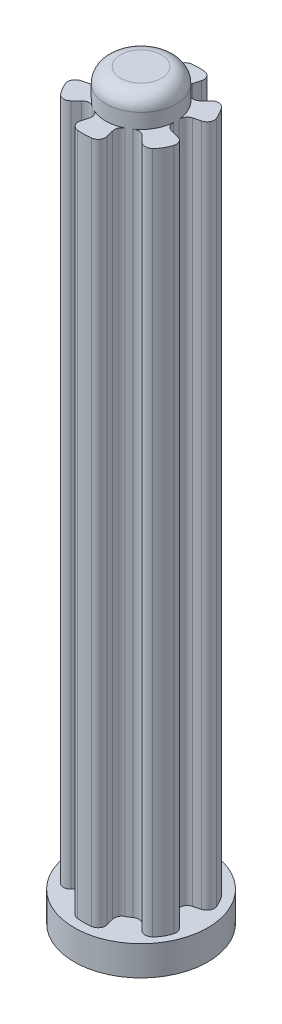
SolidWorks part; units mm, degrees
ref_plane "Front Plane" through (0, 0, 0) normal (0, 0, 1) x (1, 0, 0)
ref_plane "Top Plane" through (0, 0, 0) normal (0, 1, 0) x (1, 0, 0)
ref_plane "Right Plane" through (0, 0, 0) normal (1, 0, 0) x (0, 0, -1)
sketch "Sketch2" plane through (0, 0, 0) normal (0, 1, 0) x (1, 0, 0)
  line L0 (0, 0) -> (0.0739, 0)
  line L2 (2.3008, -0.5891) -> (3.7752, -0.9786)
  line L3 (0.0739, 0) -> (0.1042, -0.0303)
  line L4 (0, 0) -> (0.0858, -0.0446)
  line L5 (1.6802, 1.6786) -> (2.7413, 2.7388)
  line L6 (-1.6794, 1.6794) -> (-2.74, 2.74)
  line L8 (0.6147, 2.2941) -> (1.0029, 3.743)
  line L9 (-0.6147, 2.2941) -> (-1.0029, 3.743)
  line L10 (2.2941, 0.6147) -> (3.743, 1.0029)
  line L11 (0, 0) -> (0.1042, -0.0303)
  line L12 (-2.2941, 0.6147) -> (-3.743, 1.0029)
  line L13 (0.0739, 0) -> (0.0858, -0.0446)
  line L14 (-0.6147, -2.2941) -> (-1.0029, -3.743)
  line L15 (-2.2941, -0.6147) -> (-3.743, -1.0029)
  line L16 (-1.6794, -1.6794) -> (-2.74, -2.74)
  line L17 (0.6814, -2.2752) -> (1.0684, -3.7248)
  line L18 (1.7145, -1.6435) -> (2.7672, -2.6981)
  arc A0 (-2.2941, 0.6147) -> (-2.2941, -0.6147) centre (0, 0) ccw
  arc A1 (-2.74, 2.74) -> (-3.743, 1.0029) centre (0, 0) ccw
  arc A2 (1.0029, 3.743) -> (-1.0029, 3.743) centre (0, 0) ccw
  arc A3 (3.743, 1.0029) -> (2.7413, 2.7388) centre (0, 0) ccw
  arc A5 (-1.0029, -3.743) -> (1.0684, -3.7248) centre (0, 0) ccw
  arc A6 (-3.743, -1.0029) -> (-2.74, -2.74) centre (0, 0) ccw
  arc A7 (-2.74, 2.74) -> (-3.743, 1.0029) centre (0, 0) ccw
  arc A8 (1.0029, 3.743) -> (-1.0029, 3.743) centre (0, 0) ccw
  arc A9 (3.743, 1.0029) -> (2.7413, 2.7388) centre (0, 0) ccw
  arc A10 (-3.743, -1.0029) -> (-2.74, -2.74) centre (0, 0) ccw
  arc A11 (-1.0029, -3.743) -> (1.0684, -3.7248) centre (0, 0) ccw
  arc A12 (2.7672, -2.6981) -> (3.7752, -0.9786) centre (1.7753, -0.9614) ccw
  arc A13 (-0.6147, 2.2941) -> (-1.6794, 1.6794) centre (0, 0) ccw
  arc A14 (1.6802, 1.6786) -> (0.6147, 2.2941) centre (0, 0) ccw
  arc A15 (2.3008, -0.5891) -> (2.2941, 0.6147) centre (0, 0) ccw
  arc A16 (0.6814, -2.2752) -> (1.7145, -1.6435) centre (0, 0) ccw
  arc A17 (-1.6794, -1.6794) -> (-0.6147, -2.2941) centre (0, 0) ccw
  dimension "D1" = 3.875
  dimension "D2" = 2.375
extrude "Boss-Extrude1" add sketch "Sketch2" along normal blind 46 contours L16 A17 L14 A5 L17 A16 L18 A12 L2 A15 L10 A3 L5 A14 L8 A2 L9 A13 L6 A1 L12 A0 L15 A6 L11 L13 L4 L0 L3 region at (0.0225, 0, 0.0171)
sketch "Sketch3" plane through (0, 0, 0) normal (0, -1, 0) x (1, 0, 0)
  circle A0 centre (0, 0) radius 4.5
  dimension "D1" = 9
extrude "Boss-Extrude2" add sketch "Sketch3" along normal blind 2
sketch "Sketch4" plane through (0, 46, 0) normal (0, 1, 0) x (1, 0, 0)
  circle A0 centre (0, 0) radius 2.375
  dimension "D1" = 4.75
extrude "Boss-Extrude3" add sketch "Sketch4" along normal blind 2
fillet "Fillet1" radius 0.5 24 edges at (-2.74, 23, -2.74) (-1.6794, 23, -1.6794) (-0.6147, 23, -2.2941) (-1.0029, 23, -3.743) (1.0029, 23, -3.743) (0.6147, 23, -2.2941) (1.6802, 23, -1.6786) (2.7413, 23, -2.7388) (3.743, 23, -1.0029) (2.2941, 23, -0.6147) (2.3008, 23, 0.5891) (3.7752, 23, 0.9786) (2.7672, 23, 2.6981) (1.7145, 23, 1.6435) (0.6814, 23, 2.2752) (-1.6794, 23, 1.6794) (-2.2941, 23, 0.6147) (-2.2941, 23, -0.6147) (-0.6147, 23, 2.2941) (-3.743, 23, -1.0029) (-3.743, 23, 1.0029) (-2.74, 23, 2.74) (-1.0029, 23, 3.743) (1.0684, 23, 3.7248)
sketch "Sketch6" plane through (0, -2, 0) normal (0, -1, 0) x (1, 0, 0)
  circle A0 centre (0, 0) radius 1
  dimension "D1" = 2
extrude "Cut-Extrude4" cut sketch "Sketch6" against normal blind 0.5 draft 50
fillet "Fillet2" radius 1 1 edges at (0, 48, 2.375)
